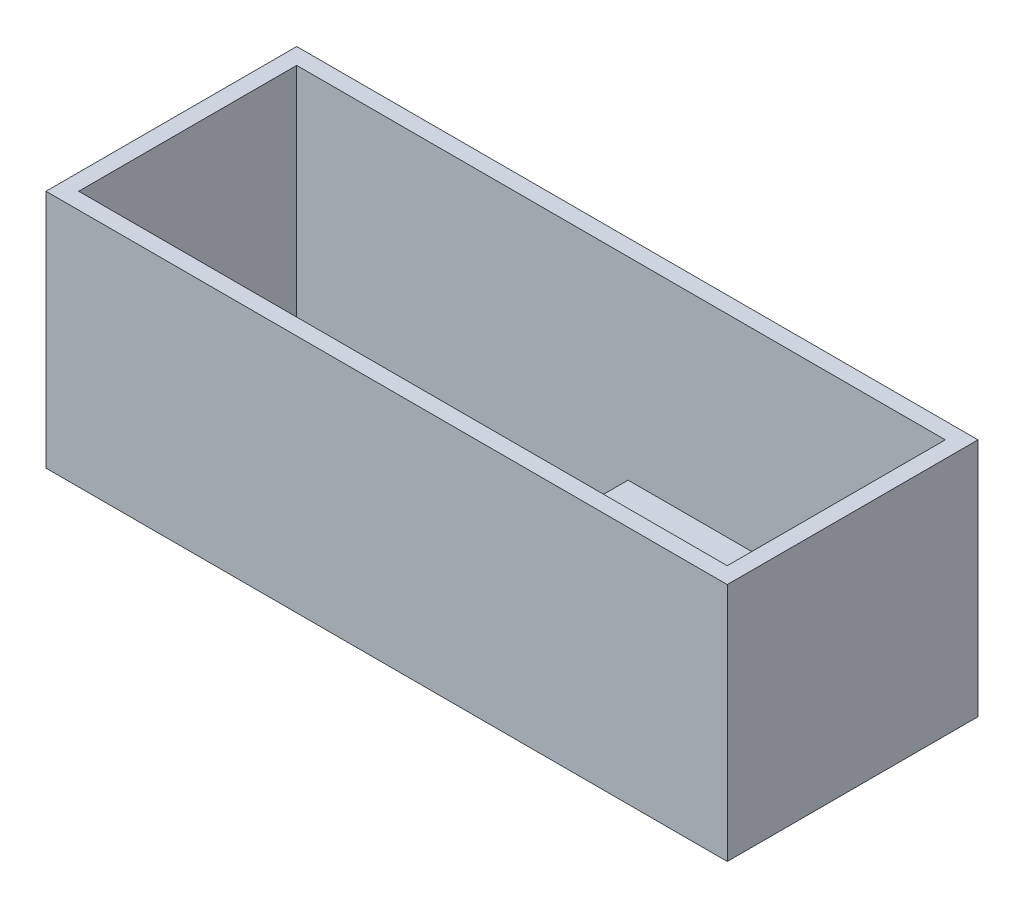
SolidWorks part; units mm, degrees
ref_plane "Front Plane" through (0, 0, 0) normal (0, 0, 1) x (1, 0, 0)
ref_plane "Top Plane" through (0, 0, 0) normal (0, 1, 0) x (1, 0, 0)
ref_plane "Right Plane" through (0, 0, 0) normal (1, 0, 0) x (0, 0, -1)
sketch "Sketch1" plane through (0, 0, 0) normal (0, 1, 0) x (1, 0, 0)
  line L1 (-59.5, -20) -> (59.5, -20)
  line L2 (-59.5, -20) -> (-59.5, 20)
  line L3 (-59.5, 20) -> (59.5, 20)
  line L4 (59.5, -20) -> (59.5, 20)
  line L5 (-59.5, -20) -> (59.5, 20) construction
  line L6 (-59.5, 20) -> (59.5, -20) construction
  point P0 (0, 0)
  dimension "D1" = 119
  dimension "D2" = 40
extrude "Boss-Extrude1" add sketch "Sketch1" along normal blind 4
sketch "Sketch2" plane through (0, 0, 0) normal (0, 1, 0) x (1, 0, 0)
  line L1 (59.5, -20) -> (-59.5, -20)
  line L2 (59.5, -20) -> (59.5, 20)
  line L3 (59.5, 20) -> (-59.5, 20)
  line L4 (-59.5, -20) -> (-59.5, 20)
  line L5 (59.5, -20) -> (-59.5, 20) construction
  line L6 (59.5, 20) -> (-59.5, -20) construction
  line L7 (-62.5, -23) -> (62.5, -23)
  line L8 (-62.5, -23) -> (-62.5, 23)
  line L9 (-62.5, 23) -> (62.5, 23)
  line L10 (62.5, -23) -> (62.5, 23)
  line L11 (-62.5, -23) -> (62.5, 23) construction
  line L12 (-62.5, 23) -> (62.5, -23) construction
  point P0 (0, 0)
  point P7 (0, 0)
  dimension "D1" = 3
  dimension "D2" = 3
extrude "Boss-Extrude2" add sketch "Sketch2" along normal blind 44
sketch "Sketch3" plane through (0, 4, 0) normal (0, 1, 0) x (1, 0, 0)
  line L0 (-59.5, -20) -> (59.5, -20) construction
  line L1 (1.3, -20) -> (59.5, -20)
  line L2 (1.3, -20) -> (1.3, 20)
  line L3 (1.3, 20) -> (59.5, 20)
  line L4 (59.5, -20) -> (59.5, 20)
  dimension "D1" = 58.2
extrude "Boss-Extrude3" add sketch "Sketch3" along normal blind 3
sketch "Sketch4" plane through (0, 7, 0) normal (0, 1, 0) x (1, 0, 0)
  line L0 (1.3, -20) -> (59.5, -20) construction
  line L1 (1.3, 20) -> (29.3, 20)
  line L2 (1.3, 20) -> (1.3, -20)
  line L3 (1.3, -20) -> (29.3, -20)
  line L4 (29.3, 20) -> (29.3, -20)
  dimension "D1" = 28
extrude "Boss-Extrude4" add sketch "Sketch4" along normal blind 1.5
sketch "Sketch5" plane through (0, 0, 0) normal (0, -1, 0) x (1, 0, 0)
  line L0 (62.5, -23) -> (-62.5, -23) construction
  line L1 (62.5, 23) -> (62.5, -23) construction
  circle A0 centre (39.5, 0) radius 4
  dimension "D1" = 8
  dimension "D2" = 23
  dimension "D3" = 23
extrude "Boss-Extrude5" add sketch "Sketch5" along normal blind 12
sketch "Sketch6" plane through (0, 0, 0) normal (0, -1, 0) x (1, 0, 0)
  circle A0 centre (39.5, 0) radius 11
  dimension "D1" = 22
extrude "Cut-Extrude1" cut sketch "Sketch6" against normal blind 3
